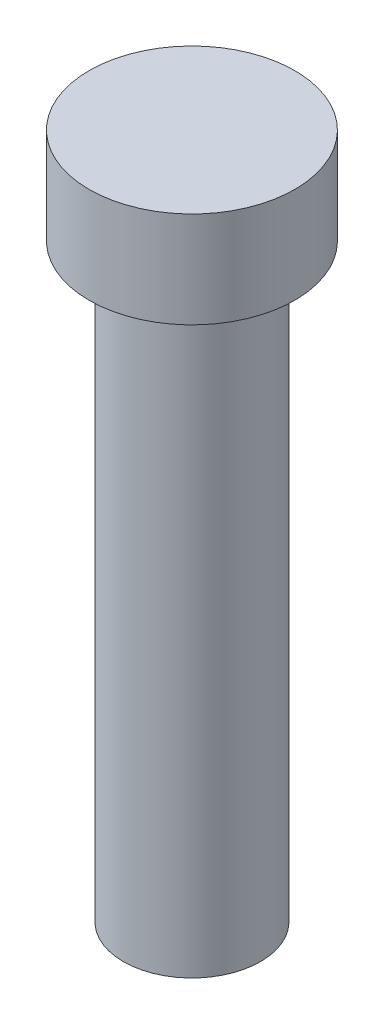
SolidWorks part; units mm, degrees
ref_plane "Front Plane" through (0, 0, 0) normal (0, 0, 1) x (1, 0, 0)
ref_plane "Top Plane" through (0, 0, 0) normal (0, 1, 0) x (1, 0, 0)
ref_plane "Right Plane" through (0, 0, 0) normal (1, 0, 0) x (0, 0, -1)
sketch "Sketch1" plane through (0, 0, 0) normal (0, 1, 0) x (1, 0, 0)
  circle A0 centre (0, 0) radius 7.5
  circle A1 centre (0, 0) radius 5
  dimension "D1" = 15
  dimension "D2" = 10
extrude "Boss-Extrude1" add sketch "Sketch1" along normal blind 7 contours A1 | A0 A1 region at (-7.2879, 0, 0) region at (0, 0, 0)
extrude "Boss-Extrude2" add sketch "Sketch1<3>" against normal blind 43 contours A1 region at (0, 0, 0)
sketch "Sketch1<3>" plane through (0, 0, 0) normal (0, 1, 0) x (1, 0, 0) same geometry as "Sketch1"
